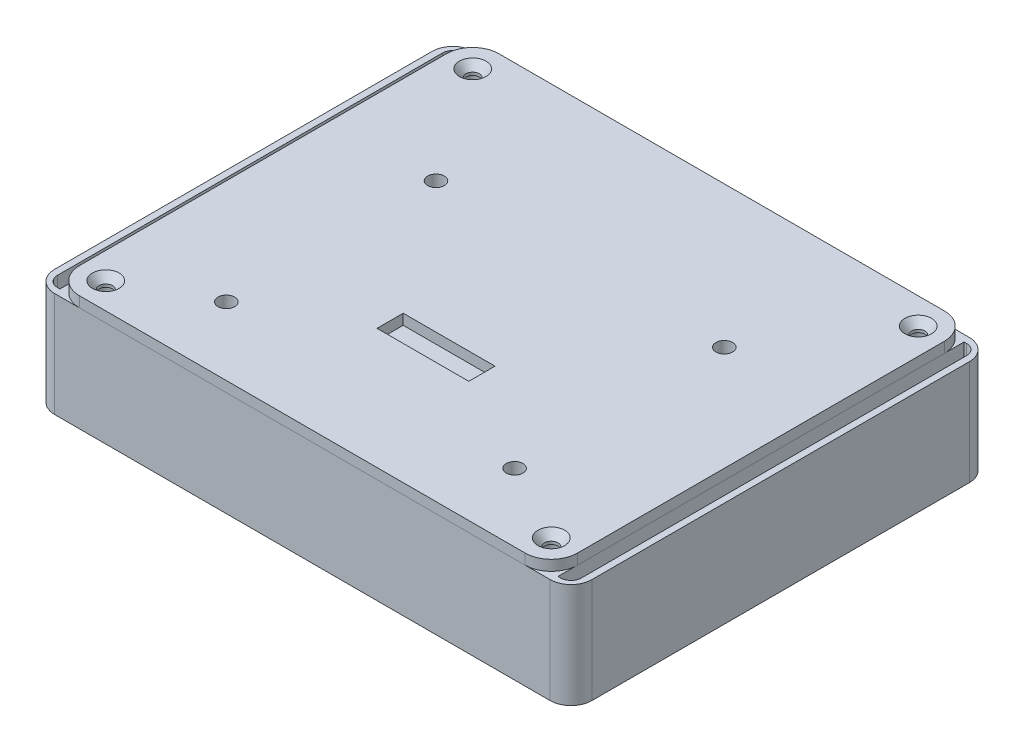
SolidWorks part; units mm, degrees
ref_plane "Front Plane" through (0, 0, 0) normal (0, 0, 1) x (1, 0, 0)
ref_plane "Top Plane" through (0, 0, 0) normal (0, 1, 0) x (1, 0, 0)
ref_plane "Right Plane" through (0, 0, 0) normal (1, 0, 0) x (0, 0, -1)
sketch "Sketch5" plane through (0, 0, 0) normal (0, 1, 0) x (1, 0, 0)
  line L0 (60.325, 50.8) -> (-60.325, -50.8) construction
  line L1 (-53.975, 50.8) -> (53.975, 50.8)
  line L2 (-60.325, 44.45) -> (-60.325, -44.45)
  line L3 (-53.975, -50.8) -> (53.975, -50.8)
  line L4 (60.325, 44.45) -> (60.325, -44.45)
  arc A0 (53.975, 50.8) -> (60.325, 44.45) centre (53.975, 44.45) cw
  arc A1 (53.975, -50.8) -> (60.325, -44.45) centre (53.975, -44.45) ccw
  arc A2 (-60.325, -44.45) -> (-53.975, -50.8) centre (-53.975, -44.45) ccw
  arc A3 (-53.975, 50.8) -> (-60.325, 44.45) centre (-53.975, 44.45) ccw
  point P4 (0, 0)
  point P11 (60.325, -50.8)
  point P17 (-60.325, 50.8)
  dimension "D3" = 6.35
  dimension "D1" = 120.65
  dimension "D2" = 101.6
extrude "Boss-Extrude2" add sketch "Sketch5" along normal blind 25.4
shell "Shell2" thickness 1.2 removed face at (0, 25.4, 0)
sketch "Sketch6" plane through (0, 1.2, 0) normal (0, 1, 0) x (1, 0, 0)
  line L0 (-59.125, 0) -> (0, 0)
  line L4 (-59.125, 49.6) -> (-53.975, 44.45) construction
  line L5 (-59.125, 44.45) -> (-59.125, -44.45) construction
  line L6 (-53.975, 49.6) -> (-50.6857, 49.6)
  line L7 (-59.125, 44.45) -> (-59.125, 41.1607)
  line L13 (-59.125, 41.1607) -> (-53.8607, 41.1607)
  line L18 (-59.125, 44.45) -> (-59.125, -44.45) construction
  line L26 (-50.6857, 49.6) -> (-50.6857, 44.3357)
  line L29 (0, 0) -> (0, 49.6)
  line L32 (-59.125, 49.6) -> (-59.125, 44.45) construction
  line L33 (53.975, 49.6) -> (-53.975, 49.6) construction
  line L34 (-53.975, 44.45) -> (0, 0) construction
  line L35 (-59.125, 49.6) -> (-53.975, 49.6) construction
  line L36 (-53.975, 42.4307) -> (-53.975, 41.1607) construction
  line L37 (-51.9557, 44.45) -> (-50.6857, 44.45) construction
  circle A8 centre (-53.975, 44.45) radius 2.0193 construction
  arc A9 (-53.975, 49.6) -> (-59.125, 44.45) centre (-53.975, 44.45) ccw construction
  arc A10 (-53.975, 49.6) -> (-59.125, 44.45) centre (-53.975, 44.45) ccw
  arc A11 (-53.8607, 41.1607) -> (-50.6857, 44.3357) centre (-53.8607, 44.3357) ccw
  point P10 (-53.975, 42.4307)
  point P11 (-51.9557, 44.45)
  point P24 (-50.6857, 41.1607)
  line M29 (-59.125, 44.45) -> (-59.125, -44.45)
  line M32 (53.975, 49.6) -> (-53.975, 49.6)
  dimension "D2" = 4.0386
  dimension "D4" = 1.27
  dimension "D1" = 3.175
extrude "Boss-Extrude3" add sketch "Sketch6" along normal up to surface (24.2 mm away) contours M32 M29 region at (-54.7495, 1.2, -45.2245) up to face at (0, 25.4, 0)
sketch "Sketch20" plane through (0, 1.2, 0) normal (0, 1, 0) x (1, 0, 0)
  line L0 (0, 0) -> (0, 49.6) construction
  line L1 (-2.0193, 44.45) -> (-3.2893, 44.45) construction
  line L2 (53.975, 49.6) -> (-50.6857, 49.6) construction
  line L3 (-3.2893, 49.6) -> (3.2893, 49.6)
  line L4 (-3.2893, 49.6) -> (-3.2893, 44.3357)
  line L5 (-0.1143, 41.1607) -> (0.1143, 41.1607)
  line L6 (3.2893, 49.6) -> (3.2893, 44.3357)
  line L7 (3.2893, 41.1607) -> (-3.2893, 49.6) construction
  line L8 (0, 42.4307) -> (0, 41.1607) construction
  line L11 (-51.9557, 44.45) -> (-50.6857, 44.45) construction
  circle A0 centre (0, 44.45) radius 2.0193 construction
  circle A1 centre (-53.975, 44.45) radius 2.0193 construction
  arc A2 (0.1143, 41.1607) -> (3.2893, 44.3357) centre (0.1143, 44.3357) ccw
  arc A3 (-3.2893, 44.3357) -> (-0.1143, 41.1607) centre (-0.1143, 44.3357) ccw
  arc A4 (-53.8607, 41.1607) -> (-50.6857, 44.3357) centre (-53.8607, 44.3357) ccw construction
  point P6 (0, 42.4307)
  point P16 (-2.0193, 44.45)
  point P17 (0, 45.3803)
extrude "Boss-Extrude8" add sketch "Sketch20" along normal up to surface (24.2 mm away) up to face at (-9.9533, 25.4, -8.0483)
sketch "Sketch8" plane through (0, 25.4, 0) normal (0, 1, 0) x (1, 0, 0)
  circle A0 centre (-53.975, 44.45) radius 2.0193 construction
  circle A1 centre (-53.975, 44.45) radius 2.0193
  circle A2 centre (0, 44.45) radius 2.0193 construction
  circle A3 centre (0, 44.45) radius 2.0193
extrude "Cut-Extrude2" cut sketch "Sketch8" against normal blind 12.7
mirror "Mirror1" about plane through (0, 0, 0) normal (1, 0, 0) of "Cut-Extrude2", "Boss-Extrude3"
mirror "Mirror2" about plane through (0, 0, 0) normal (0, 0, 1) of "Mirror1", "Boss-Extrude8", "Boss-Extrude3"
sketch "Sketch2" plane through (0, 1.2, 0) normal (0, 1, 0) x (1, 0, 0)
  line L3 (-29.4873, -38.1) -> (-9.9293, -38.1) construction
  line L4 (-13.0863, -42.418) -> (-13.0863, -33.782) construction
  line L5 (-59.125, 0) -> (-19.7083, 0)
  line L6 (-59.125, 0) -> (0, 0) construction
  line L7 (-19.7083, 0) -> (19.7083, 0)
  line L8 (19.7083, 0) -> (59.125, 0)
  line L9 (59.125, -41.1607) -> (59.125, 41.1607) construction
  line L10 (-19.7083, -38.1) -> (-19.7083, 0) construction
  line L12 (-9.9293, -36.9389) -> (-13.0863, -33.782) construction
  line L13 (-13.0863, -33.782) -> (-28.9793, -33.782) construction
  line L14 (-29.4873, -34.29) -> (-29.4873, -41.91) construction
  line L15 (-28.9793, -42.418) -> (-13.0863, -42.418) construction
  line L16 (-13.0863, -42.418) -> (-9.9293, -39.2611) construction
  line L17 (-9.9293, -39.2611) -> (-9.9293, -36.9389) construction
  line L18 (-9.5483, -36.7811) -> (-12.9285, -33.401)
  line L19 (-12.9285, -33.401) -> (-28.9793, -33.401)
  line L20 (-29.8683, -34.29) -> (-29.8683, -41.91)
  line L21 (-28.9793, -42.799) -> (-12.9285, -42.799)
  line L22 (-12.9285, -42.799) -> (-9.5483, -39.4189)
  line L23 (-9.5483, -39.4189) -> (-9.5483, -36.7811)
  line L24 (9.9293, -38.1) -> (29.4873, -38.1) construction
  line L25 (26.3304, -42.418) -> (26.3304, -33.782) construction
  line L26 (29.4873, -36.9389) -> (26.3304, -33.782) construction
  line L27 (26.3304, -33.782) -> (10.4373, -33.782) construction
  line L28 (9.9293, -34.29) -> (9.9293, -41.91) construction
  line L29 (10.4373, -42.418) -> (26.3304, -42.418) construction
  line L30 (26.3304, -42.418) -> (29.4873, -39.2611) construction
  line L31 (29.4873, -39.2611) -> (29.4873, -36.9389) construction
  line L38 (19.7083, -38.1) -> (19.7083, 0) construction
  line L39 (29.8683, -36.7811) -> (26.4882, -33.401)
  line L40 (26.4882, -33.401) -> (10.4373, -33.401)
  line L41 (9.5483, -34.29) -> (9.5483, -41.91)
  line L42 (10.4373, -42.799) -> (26.4882, -42.799)
  line L43 (26.4882, -42.799) -> (29.8683, -39.4189)
  line L44 (29.8683, -39.4189) -> (29.8683, -36.7811)
  arc A2 (-28.9793, -33.401) -> (-29.8683, -34.29) centre (-28.9793, -34.29) ccw
  arc A3 (-29.8683, -41.91) -> (-28.9793, -42.799) centre (-28.9793, -41.91) ccw
  arc A4 (-28.9793, -33.782) -> (-29.4873, -34.29) centre (-28.9793, -34.29) ccw construction
  arc A5 (-29.4873, -41.91) -> (-28.9793, -42.418) centre (-28.9793, -41.91) ccw construction
  arc A8 (10.4373, -33.782) -> (9.9293, -34.29) centre (10.4373, -34.29) ccw construction
  arc A9 (9.9293, -41.91) -> (10.4373, -42.418) centre (10.4373, -41.91) ccw construction
  arc A10 (10.4373, -33.401) -> (9.5483, -34.29) centre (10.4373, -34.29) ccw
  arc A11 (9.5483, -41.91) -> (10.4373, -42.799) centre (10.4373, -41.91) ccw
  dimension "D3" = 0.508
  dimension "D9" = 19.558
  dimension "D10" = 0.508
  dimension "D1" = 8.636
  dimension "D2" = 19.558
  dimension "D4" = 2.3221
  dimension "D5" = 16.4011
  dimension "D6" = 38.1
  dimension "D7" = 0.381
  dimension "D8" = 8.636
  dimension "D11" = 2.3221
  dimension "D12" = 16.4011
  dimension "D13" = 0.381
extrude "Cut-Extrude3" cut sketch "Sketch2" against normal blind 12.7 contours L20 A3 L21 L22 L23 L18 L19 A2 | L41 A11 L42 L43 L44 L39 L40 A10 region at (-20.2654, 1.2, 38.1) region at (19.1513, 1.2, 38.1)
ref_plane "Plane2" through (0, 0, 38.1) normal (0, 0, 1) x (1, 0, 0)
ref_plane "Plane3" through (19.7083, 0, 0) normal (1, 0, 0) x (0, 0, -1)
ref_plane "Plane4" through (-19.7083, 0, 0) normal (1, 0, 0) x (0, 0, -1)
sketch "Sketch9" plane through (0, 1.2, 0) normal (0, 1, 0) x (1, 0, 0)
  line L0 (50.3883, -27.2607) -> (56.9923, -38.6907) construction
  line L1 (50.3883, -38.6907) -> (50.3883, -27.2607) construction
  line L2 (50.3883, -38.6907) -> (56.9923, -38.6907) construction
  line L3 (56.9923, -38.6907) -> (56.9923, -27.2607) construction
  line L4 (50.3883, -27.2607) -> (56.9923, -27.2607) construction
  line L5 (49.1183, -38.6907) -> (49.1183, -27.2607)
  line L6 (50.3883, -25.9907) -> (56.9923, -25.9907)
  line L7 (58.2623, -38.6907) -> (58.2623, -27.2607)
  line L8 (50.3883, -39.9607) -> (56.9923, -39.9607)
  line L9 (49.1183, -39.9607) -> (49.1183, -25.9907) construction
  line L10 (49.1183, -25.9907) -> (58.2623, -25.9907) construction
  line L11 (58.2623, -39.9607) -> (58.2623, -25.9907) construction
  line L12 (49.1183, -39.9607) -> (58.2623, -39.9607) construction
  line L13 (53.8607, -41.1607) -> (59.125, -41.1607) construction
  line L14 (59.125, -41.1607) -> (59.125, 41.1607) construction
  arc A0 (49.1183, -27.2607) -> (50.3883, -25.9907) centre (50.3883, -27.2607) cw
  arc A1 (56.9923, -25.9907) -> (58.2623, -27.2607) centre (56.9923, -27.2607) cw
  arc A2 (58.2623, -38.6907) -> (56.9923, -39.9607) centre (56.9923, -38.6907) cw
  arc A3 (49.1183, -38.6907) -> (50.3883, -39.9607) centre (50.3883, -38.6907) ccw
  dimension "D4" = 1.27
  dimension "D1" = 11.43
  dimension "D2" = 6.604
  dimension "D5" = 1.2
  dimension "D6" = 0.8627
  dimension "D3" = 1.27
extrude "Cut-Extrude4" cut sketch "Sketch9" against normal through all
sketch "Sketch10" plane through (0, 25.4, 0) normal (0, 1, 0) x (1, 0, 0)
  line L4 (53.975, 50.8) -> (-53.975, 50.8)
  line L5 (-60.325, 44.45) -> (-60.325, -44.45)
  line L6 (-53.975, -50.8) -> (53.975, -50.8)
  line L7 (60.325, -44.45) -> (60.325, 44.45)
  line L8 (53.975, 50.8) -> (-53.975, 50.8)
  line L9 (-60.325, 44.45) -> (-60.325, -44.45)
  line L10 (-53.975, -50.8) -> (53.975, -50.8)
  line L11 (60.325, -44.45) -> (60.325, 44.45)
  arc A4 (60.325, 44.45) -> (53.975, 50.8) centre (53.975, 44.45) ccw
  arc A5 (-53.975, 50.8) -> (-60.325, 44.45) centre (-53.975, 44.45) ccw
  arc A6 (-60.325, -44.45) -> (-53.975, -50.8) centre (-53.975, -44.45) ccw
  arc A7 (53.975, -50.8) -> (60.325, -44.45) centre (53.975, -44.45) ccw
  arc A8 (60.325, 44.45) -> (53.975, 50.8) centre (53.975, 44.45) ccw
  arc A9 (-53.975, 50.8) -> (-60.325, 44.45) centre (-53.975, 44.45) ccw
  arc A10 (-60.325, -44.45) -> (-53.975, -50.8) centre (-53.975, -44.45) ccw
  arc A11 (53.975, -50.8) -> (60.325, -44.45) centre (53.975, -44.45) ccw
  dimension "D1" = 0
extrude "Boss-Extrude4" add sketch "Sketch10" along normal blind 2.54 separate body
hole_wizard "CSK for #4 Flat Head Machine Screw1" positions "Sketch11" profile "Sketch12" countersink size "#4" standard "ANSI Inch" end condition up to next
sketch "Sketch11" plane through (0, 27.94, 0) normal (0, 1, 0) x (1, 0, 0)
  point P0 (-53.975, 44.45)
sketch "Sketch12" plane through (-53.975, 27.94, -44.45) normal (1, 0, 0) x (0, 0, 1)
  line L0 (0, 0) -> (0, 27.94)
  line L1 (0, 27.94) -> (1.6319, 27.94)
  line L2 (1.6319, 27.94) -> (1.6319, 1.8481)
  line L3 (1.6319, 1.8481) -> (3.2385, 0)
  line L5 (3.2385, 0) -> (0, 0)
  line L6 (-1.6319, 1.8481) -> (-3.2385, 0) construction
  line L11 (0, -6.35) -> (0, 107.95) construction
  dimension "Thru Hole Dia." = 3.2639
  dimension "Thru Hole Depth" = 27.94
  dimension "Near C'Sink Dia." = 6.477
  dimension "Near C'Sink Angle" = 82
mirror "Mirror3" about plane through (0, 0, 0) normal (0, 0, 1) of "CSK for #4 Flat Head Machine Screw1"
mirror "Mirror4" about plane through (0, 0, 0) normal (1, 0, 0) of "CSK for #4 Flat Head Machine Screw1", "Mirror3"
sketch "Sketch13" plane through (0, 27.94, 0) normal (0, 1, 0) x (1, 0, 0)
  line L0 (34.925, -34.29) -> (-34.925, 16.51) construction
  line L1 (-34.925, 16.51) -> (34.925, 16.51) construction
  line L2 (-34.925, 16.51) -> (-34.925, -34.29) construction
  line L3 (-34.925, -34.29) -> (34.925, -34.29) construction
  line L4 (34.925, 16.51) -> (34.925, -34.29) construction
  line L5 (11.1125, -15.24) -> (-11.1125, -21.59) construction
  line L6 (-11.1125, -15.24) -> (11.1125, -15.24)
  line L7 (-11.1125, -15.24) -> (-11.1125, -21.59)
  line L8 (-11.1125, -21.59) -> (11.1125, -21.59)
  line L9 (11.1125, -15.24) -> (11.1125, -21.59)
  line L10 (0, -18.415) -> (0, -8.89) construction
  line L11 (0, 0) -> (0, -8.89) construction
  circle A0 centre (-34.925, -34.29) radius 2.0193 construction
  circle A1 centre (34.925, -34.29) radius 2.0193 construction
  circle A2 centre (34.925, 16.51) radius 2.0193 construction
  circle A3 centre (-34.925, 16.51) radius 2.0193 construction
  point P5 (0, 0)
  dimension "D3" = 4.0386
  dimension "D1" = 69.85
  dimension "D2" = 50.8
  dimension "D4" = 6.35
  dimension "D5" = 22.225
  dimension "D6" = 8.89
  dimension "D7" = 9.525
sketch "Sketch14" plane through (0, 25.4, 0) normal (0, -1, 0) x (1, 0, 0)
  circle A0 centre (-34.925, 34.29) radius 3.6193
  circle A1 centre (-34.925, -16.51) radius 3.6193
  circle A2 centre (34.925, -16.51) radius 3.6193
  circle A4 centre (34.925, 34.29) radius 3.6193
  circle A5 centre (-34.925, 34.29) radius 2.0193 construction
  dimension "D1" = 1.6
extrude "Boss-Extrude6" add sketch "Sketch14" along normal offset from surface (0.889 mm away) 3.429 contours A0 | A1 | A2 | A4 up to face at (53.975, 27.94, 47.6885)
sketch "Sketch16" plane through (0, 27.94, 0) normal (0, 1, 0) x (1, 0, 0)
  line L0 (11.1125, -15.24) -> (11.1125, -21.59) construction
  line L5 (-11.1125, -21.59) -> (11.1125, -21.59) construction
  line L6 (-11.1125, -15.24) -> (-11.1125, -21.59) construction
  line L7 (-11.1125, -15.24) -> (11.1125, -15.24) construction
  line L8 (11.1125, -15.24) -> (11.1125, -21.59)
  line L9 (-11.1125, -21.59) -> (11.1125, -21.59)
  line L10 (-11.1125, -15.24) -> (-11.1125, -21.59)
  line L11 (-11.1125, -15.24) -> (11.1125, -15.24)
  circle A0 centre (34.925, 16.51) radius 2.0193 construction
  circle A1 centre (34.925, -34.29) radius 2.0193 construction
  circle A2 centre (-34.925, -34.29) radius 2.0193 construction
  circle A3 centre (-34.925, 16.51) radius 2.0193 construction
  circle A4 centre (34.925, 16.51) radius 2.0193
  circle A5 centre (34.925, -34.29) radius 2.0193
  circle A6 centre (-34.925, -34.29) radius 2.0193
  circle A7 centre (-34.925, 16.51) radius 2.0193
extrude "Cut-Extrude5" cut sketch "Sketch16" against normal through all
sketch "Sketch18" plane through (0, 0, 0) normal (0, -1, 0) x (1, 0, 0)
  line L0 (-53.975, -50.8) -> (-65.1, -50.8)
  line L1 (-60.325, -49.2) -> (-63.5, -49.2)
  line L2 (-65.1, -50.8) -> (-65.1, 50.8)
  line L3 (-65.1, 50.8) -> (-53.975, 50.8)
  line L4 (-60.325, 49.2) -> (-63.5, 49.2)
  line L5 (-63.5, 49.2) -> (-63.5, -49.2)
  line L6 (-61.9125, 49.2) -> (-61.9125, 50.8) construction
  line L7 (-65.1, 0) -> (-63.5, 0) construction
  line L8 (-61.9125, -49.2) -> (-61.9125, -50.8) construction
  line L9 (-60.325, -44.45) -> (-60.325, 44.45) construction
  line L10 (-60.325, -44.45) -> (-60.325, -49.2)
  line L11 (-60.325, 44.45) -> (-60.325, 49.2)
  arc A4 (-60.325, -44.45) -> (-53.975, -50.8) centre (-53.975, -44.45) ccw construction
  arc A5 (-60.325, -44.45) -> (-53.975, -50.8) centre (-53.975, -44.45) ccw
  arc A6 (-53.975, 50.8) -> (-60.325, 44.45) centre (-53.975, 44.45) ccw construction
  arc A7 (-53.975, 50.8) -> (-60.325, 44.45) centre (-53.975, 44.45) ccw
  point P2 (-57.15, 50.8)
  dimension "D1" = 1.6
  dimension "D2" = 3.175
extrude "Boss-Extrude7" add sketch "Sketch18" against normal up to surface (25.4 mm away) up to face at (53.975, 25.4, 42.4307)
fillet "Fillet3" radius 5.08 2 edges at (-65.1, 12.7, 50.8) (-65.1, 12.7, -50.8)
fillet "Fillet4" radius 2.54 2 edges at (-63.5, 12.7, 49.2) (-63.5, 12.7, -49.2)
mirror "Mirror5" about plane through (0, 0, 0) normal (1, 0, 0) of "Fillet3", "Fillet4", "Boss-Extrude7"
fillet "Fillet6" radius 3.175 4 edges at (-3.2893, 13.3, 49.6) (3.2893, 13.3, 49.6) (3.2893, 13.3, -49.6) (-3.2893, 13.3, -49.6)
